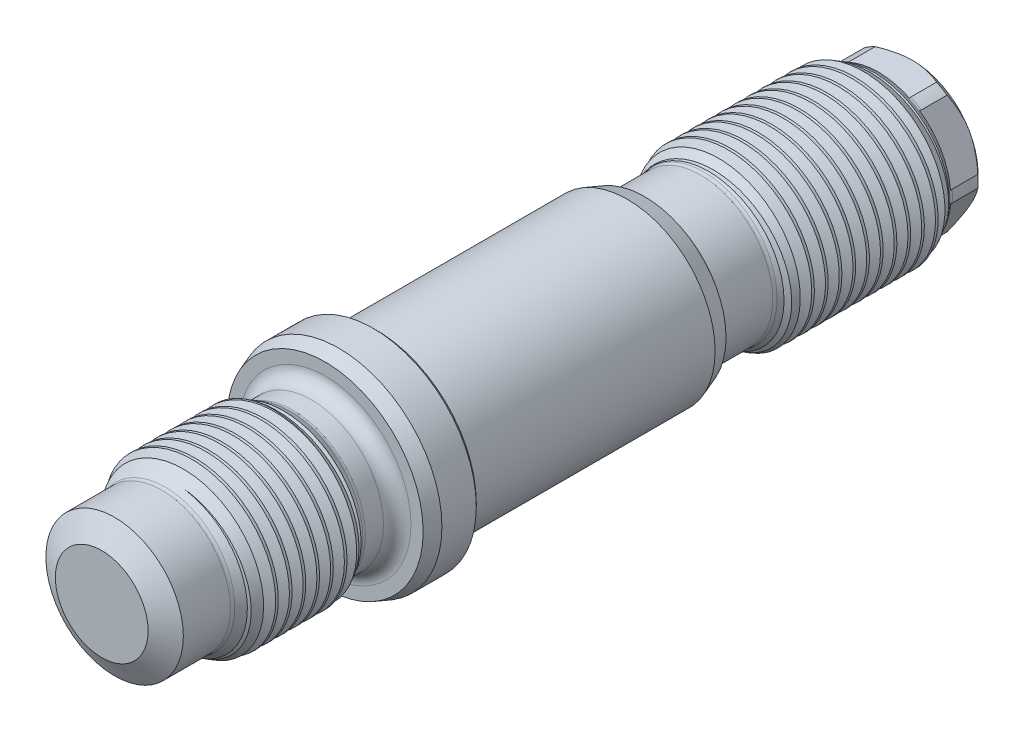
SolidWorks part; units mm, degrees
ref_plane "Front" through (0, 0, 0) normal (0, 0, 1) x (1, 0, 0)
ref_plane "Top" through (0, 0, 0) normal (0, 1, 0) x (1, 0, 0)
ref_plane "Right" through (0, 0, 0) normal (1, 0, 0) x (0, 0, -1)
sketch "Sketch1" plane through (0, 0, 0) normal (1, 0, 0) x (0, 0, -1)
  line L0 (0, 0) -> (114.0536, 0)
  line L1 (0, 0) -> (0, 6.75)
  line L2 (0, 6.75) -> (1.8764, 10)
  line L3 (1.8764, 10) -> (8.7321, 10)
  line L4 (9.2321, 10.134) -> (12.4641, 12)
  line L5 (12.4641, 12) -> (25, 12)
  line L6 (25, 12) -> (27.366, 10.634)
  line L7 (27.866, 10.5) -> (30.5, 10.5)
  line L8 (32.5, 12.5) -> (32.5, 14.2721)
  line L9 (32.5, 14.2721) -> (34.5, 15)
  line L10 (34.5, 15) -> (39.5, 15)
  line L11 (40, 14.5) -> (40, 13.75)
  line L12 (41, 12.75) -> (76.5, 12.75)
  line L13 (118, 3.075) -> (118, 9.5)
  line L14 (118, 9.5) -> (117, 10.5)
  line L15 (117, 10.5) -> (113.2679, 10.5)
  line L16 (112.7679, 10.634) -> (110.4019, 12)
  line L17 (110.4019, 12) -> (90, 12)
  line L18 (90, 12) -> (87.634, 10.634)
  line L19 (87.134, 10.5) -> (80, 10.5)
  line L20 (79, 11.5) -> (79, 11.8401)
  line L21 (79, 11.8401) -> (76.5, 12.75)
  line L22 (39.5, 15) -> (40, 14.5)
  line L23 (0, 0) -> (118, 0) construction
  line L24 (118, 3.075) -> (116.5, 1.575)
  line L25 (116.5, 1.575) -> (115, 1.575)
  line L26 (115, 1.575) -> (114.0536, 0)
  arc A0 (8.7321, 10) -> (9.2321, 10.134) centre (8.7321, 11) ccw
  arc A1 (27.366, 10.634) -> (27.866, 10.5) centre (27.866, 11.5) ccw
  arc A2 (40, 13.75) -> (41, 12.75) centre (41, 13.75) ccw
  arc A3 (113.2679, 10.5) -> (112.7679, 10.634) centre (113.2679, 11.5) cw
  arc A4 (80, 10.5) -> (79, 11.5) centre (80, 11.5) cw
  arc A5 (87.634, 10.634) -> (87.134, 10.5) centre (87.134, 11.5) cw
  arc A6 (30.5, 10.5) -> (32.5, 12.5) centre (30.5, 12.5) ccw
  point P25 (9, 10)
  point P32 (113, 10.5)
  dimension "D28" = 1
  dimension "D29" = 2
  dimension "D2" = 30
  dimension "D3" = 6.75
  dimension "D4" = 10
  dimension "D5" = 12
  dimension "D6" = 9
  dimension "D7" = 30
  dimension "D8" = 25
  dimension "D9" = 30
  dimension "D10" = 10.5
  dimension "D11" = 32.5
  dimension "D12" = 20
  dimension "D13" = 2
  dimension "D14" = 7.5
  dimension "D15" = 15
  dimension "D16" = 12.75
  dimension "D17" = 12
  dimension "D18" = 10.5
  dimension "D19" = 1
  dimension "D20" = 45
  dimension "D21" = 5
  dimension "D22" = 30
  dimension "D23" = 30
  dimension "D24" = 28
  dimension "D25" = 20
  dimension "D26" = 2.5
  dimension "D27" = 39
  dimension "D30" = 0.5
  dimension "D31" = 45
  dimension "D32" = 59
  dimension "D33" = 45
  dimension "D34" = 3
  dimension "D35" = 1.5
  dimension "D36" = 1.575
  dimension "D37" = 118
revolve "Revolve1" add sketch "Sketch1" angle 360 about L0
ref_plane "Plane1" through (0, 0, -118) normal (0, 0, -1) x (-1, 0, 0)
sketch "Sketch2" plane through (0, 0, 0) normal (0, 0, 1) x (1, 0, 0)
  circle A0 centre (0, 0) radius 12
  dimension "D1" = 24
curve "Helix/Spiral1" pitch 2 height 28 radius 12 centre (0, 0, 0) axis (0, 0, -1) start towards (0, 1, 0)
sketch "Sketch3" plane through (0, 0, 0) normal (1, 0, 0) x (0, 0, -1)
  line L0 (0, 10.6) -> (0.99, 12.3147)
  line L1 (0.99, 12.3147) -> (-0.99, 12.3147)
  line L2 (-0.99, 12.3147) -> (0, 10.6)
  dimension "D1" = 60
  dimension "D2" = 60
  dimension "D3" = 1.98
  dimension "D4" = 10.6
sweep "Cut-Sweep1" cut profiles "Sketch3" path "Helix/Spiral1" align with end faces yes
sketch "Sketch4" plane through (0, 0, -118) normal (0, 0, -1) x (-1, 0, 0)
  circle A0 centre (0, 0) radius 12
  dimension "D1" = 24
curve "Helix/Spiral2" pitch 2 height 34 radius 12 centre (0, 0, -118) axis (0, 0, 1) start towards (0, 1, 0)
sketch "Sketch5" plane through (0, 0, 0) normal (1, 0, 0) x (0, 0, -1)
  line L0 (118, 10.6) -> (118.99, 12.3147)
  line L1 (118.99, 12.3147) -> (117.01, 12.3147)
  line L2 (117.01, 12.3147) -> (118, 10.6)
  line L3 (0, 0) -> (118, 0) construction
  dimension "D1" = 1.98
  dimension "D2" = 60
  dimension "D3" = 60
  dimension "D4" = 118
  dimension "D5" = 10.6
sweep "Cut-Sweep2" cut profiles "Sketch5" path "Helix/Spiral2" align with end faces yes
sketch "Sketch6" plane through (0, 0, -118) normal (0, 0, -1) x (-1, 0, 0)
  line L1 (-10.9697, 0) -> (-5.4848, -9.5)
  line L2 (-5.4848, -9.5) -> (5.4848, -9.5)
  line L3 (5.4848, -9.5) -> (10.9697, 0)
  line L4 (10.9697, 0) -> (5.4848, 9.5)
  line L5 (5.4848, 9.5) -> (-5.4848, 9.5)
  line L6 (-5.4848, 9.5) -> (-10.9697, 0)
  circle A0 centre (0, 0) radius 9.5 construction
  dimension "D1" = 19
extrude "Cut-Extrude1" cut sketch "Sketch6" against normal blind 5 flip side to cut
